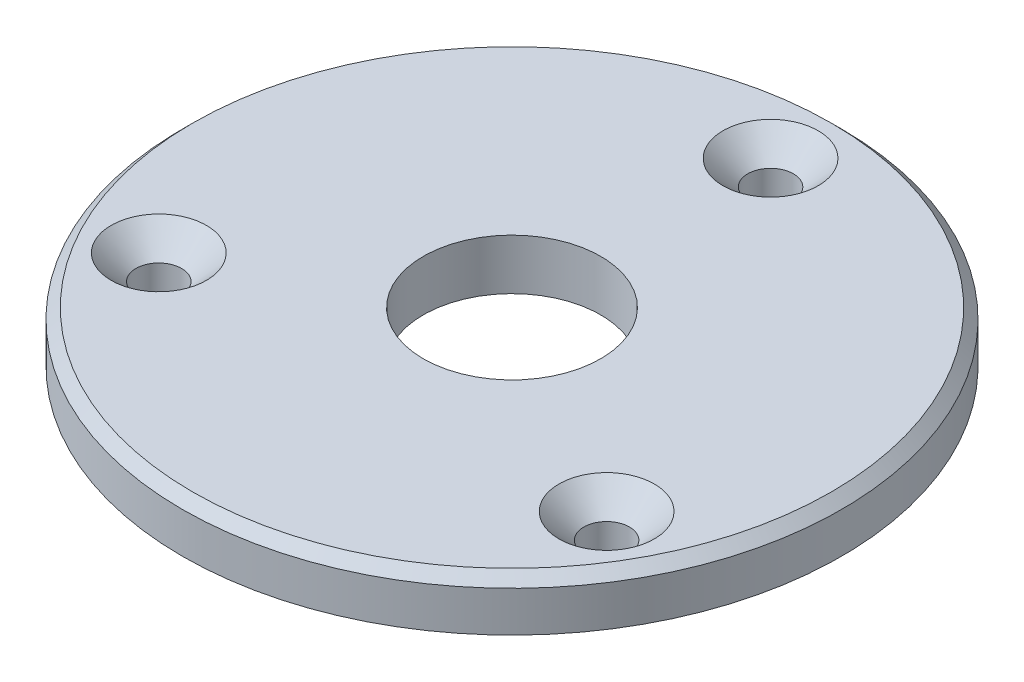
SolidWorks part; units mm, degrees
ref_plane "Front Plane" through (0, 0, 0) normal (0, 0, 1) x (1, 0, 0)
ref_plane "Top Plane" through (0, 0, 0) normal (0, 1, 0) x (1, 0, 0)
ref_plane "Right Plane" through (0, 0, 0) normal (1, 0, 0) x (0, 0, -1)
sketch "Sketch1" plane through (0, 0, 0) normal (0, 1, 0) x (1, 0, 0)
  circle A1 centre (0, 0) radius 32.5
  dimension "D1" = 65
extrude "Boss-Extrude1" add sketch "Sketch1" along normal blind 5
chamfer "Chamfer1" distance 1 angle 45 1 edges at (0, 5, 32.5)
sketch "Sketch2" plane through (0, 5, 0) normal (0, 1, 0) x (1, 0, 0)
  line L0 (0, 5.75) -> (0, 31.5) construction
  circle A2 centre (0, 0) radius 5.75
  circle A3 centre (0, 0) radius 31.5 construction
  point P7 (0, 25.5)
  dimension "D1" = 11.5
  dimension "D2" = 6
hole_wizard "CSK for M4 Countersunk Flat Head1" positions "3DSketch1" profile "Sketch3" countersink size "M4" standard "BSI" end condition through all
sketch3d "3DSketch1"
  point P0 (0, 5, -25.5)
sketch "Sketch3" plane through (0, 5, -25.5) normal (1, 0, 0) x (0, 0, 1)
  line L0 (0, 0) -> (0, 5)
  line L1 (0, 5) -> (2.25, 5)
  line L2 (2.25, 5) -> (2.25, 2.45)
  line L3 (2.25, 2.45) -> (4.7, 0)
  line L5 (4.7, 0) -> (0, 0)
  line L6 (-2.25, 2.45) -> (-4.7, 0) construction
  line L11 (0, -6.35) -> (0, 107.95) construction
  dimension "Thru Hole Dia." = 4.5
  dimension "Thru Hole Depth" = 5
  dimension "Near C'Sink Dia." = 9.4
  dimension "Near C'Sink Angle" = 90
hole_wizard "M20x2.5 Tapped Hole1" positions "3DSketch2" profile "Sketch4" tap size "M20x2.5" standard "BSI" end condition through all
sketch3d "3DSketch2"
  point P0 (0, 0, 0)
  point P3 (0, 5, 0)
cosmetic thread "Hole Thread1" parameters "D2"=20
cosmetic thread "Hole Thread2" parameters "D2"=20
sketch "Sketch4" plane through (0, 5, 0) normal (1, 0, 0) x (0, 0, 1)
  line L0 (0, 0) -> (0, 5)
  line L1 (0, 5) -> (8.75, 5)
  line L2 (8.75, 5) -> (8.75, 0)
  line L5 (8.75, 0) -> (0, 0)
  line L11 (0, -6.35) -> (0, 107.95) construction
  dimension "Thru Tap Drill Dia." = 17.5
  dimension "Thru Tap Drill Depth" = 5
pattern_circular "CirPattern1" count 3 over 360 about axis through (0, 5, 0) along (0, 1, 0) of "CSK for M4 Countersunk Flat Head1" reverse direction yes
